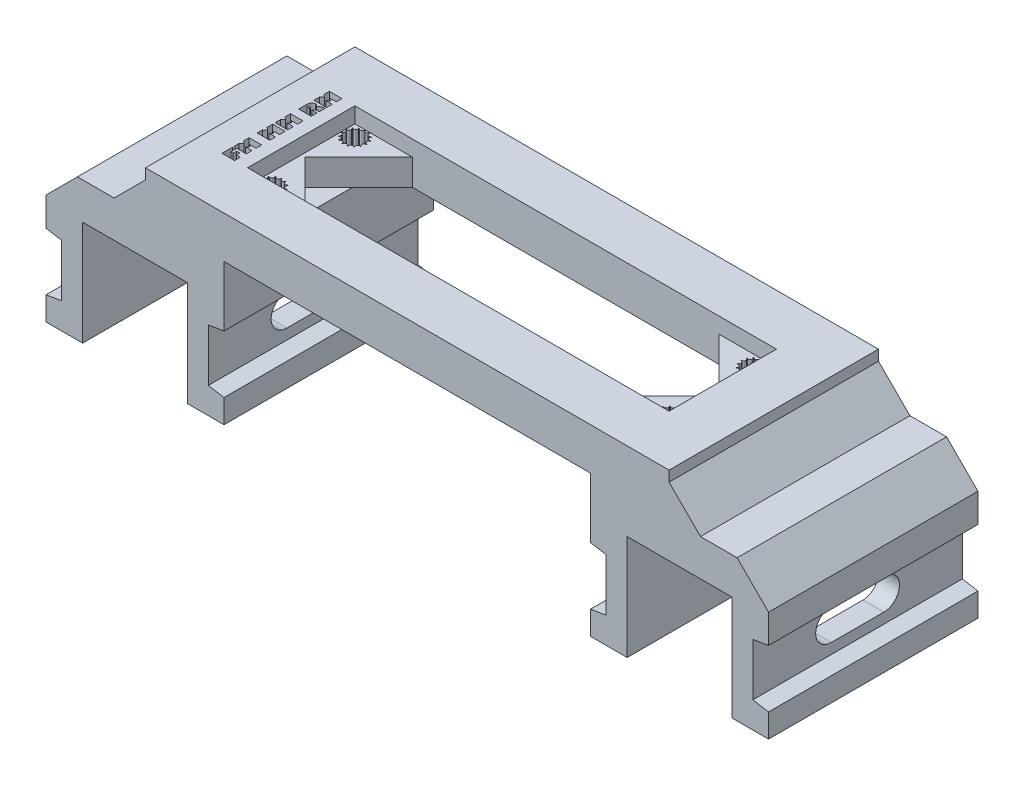
SolidWorks part; units mm, degrees
ref_plane "Front Plane" through (0, 0, 0) normal (0, 0, 1) x (1, 0, 0)
ref_plane "Top Plane" through (0, 0, 0) normal (0, 1, 0) x (1, 0, 0)
ref_plane "Right Plane" through (0, 0, 0) normal (1, 0, 0) x (0, 0, -1)
sketch "Sketch1" plane through (0, 0, 0) normal (0, 1, 0) x (1, 0, 0)
  line L1 (0, 0) -> (80, 0)
  line L2 (0, 0) -> (0, 20)
  line L3 (0, 20) -> (80, 20)
  line L4 (80, 0) -> (80, 20)
  dimension "D1" = 20
  dimension "D2" = 80
extrude "Boss-Extrude1" add sketch "Sketch1" along normal blind 8
sketch "Sketch2" plane through (0, 8, 0) normal (0, 1, 0) x (1, 0, 0)
  line L0 (0, 0) -> (80, 0) construction
  line L1 (0, 10) -> (80, 10) construction
  line L2 (0, 20) -> (0, 0) construction
  line L3 (5.4641, 0) -> (0, 0)
  line L4 (0, 0) -> (0, 5.4641)
  line L5 (80, 0) -> (80, 20) construction
  line L6 (80, 10) -> (40, 10) construction
  line L7 (40, 10) -> (40, 20) construction
  line L8 (80, 20) -> (0, 20) construction
  line L13 (0, 20) -> (0, 0)
  line L14 (0, 0) -> (80, 0)
  line L15 (80, 0) -> (80, 20)
  line L16 (80, 20) -> (0, 20)
  line L17 (0, 20) -> (0, 0)
  line L18 (0, 0) -> (80, 0)
  line L19 (80, 0) -> (80, 20)
  line L20 (80, 20) -> (0, 20)
  circle A0 centre (2, 2) radius 2.25
  arc A1 (5.4641, 0) -> (0, 5.4641) centre (2, 2) ccw
  arc A2 (5.4641, 20) -> (0, 14.5359) centre (2, 18) cw
  circle A3 centre (2, 18) radius 2.25
  arc A4 (74.5359, 20) -> (80, 14.5359) centre (78, 18) ccw
  arc A5 (74.5359, 0) -> (80, 5.4641) centre (78, 2) cw
  circle A6 centre (-0.25, 2) radius 0.4
  circle A7 centre (-0.0555, 2.9152) radius 0.4
  circle A8 centre (0.4945, 3.6721) radius 0.4
  circle A9 centre (1.3047, 4.1399) radius 0.4
  circle A10 centre (2.2352, 4.2377) radius 0.4
  circle A11 centre (3.125, 3.9486) radius 0.4
  circle A12 centre (3.8203, 3.3225) radius 0.4
  circle A13 centre (4.2008, 2.4678) radius 0.4
  circle A14 centre (4.2008, 1.5322) radius 0.4
  circle A15 centre (3.8203, 0.6775) radius 0.4
  circle A16 centre (3.125, 0.0514) radius 0.4
  circle A17 centre (2.2352, -0.2377) radius 0.4
  circle A18 centre (1.3047, -0.1399) radius 0.4
  circle A19 centre (0.4945, 0.3279) radius 0.4
  circle A20 centre (-0.0555, 1.0848) radius 0.4
  point P64 (2, 2)
  line M11 (0, 20) -> (0, 0)
  line M12 (0, 0) -> (80, 0)
  dimension "D1" = 4.5
  dimension "D4" = 8
  dimension "D6" = 0.8
  dimension "D2" = 2
  dimension "D3" = 2
  dimension "D5" = 0
  dimension "D7" = 15
extrude "Cut-Extrude1" cut sketch "Sketch2" against normal blind 8 contours A5 L19 A4 L20 A2 L17 A1 M12 region at (40, 8, -10)
sketch "Sketch3" plane through (0, 8, 0) normal (0, 1, 0) x (1, 0, 0)
  line L0 (90, -10) -> (90, 30)
  line L1 (80, 0) -> (0, 0)
  line L2 (80, 0) -> (80, 20)
  line L3 (80, 20) -> (0, 20)
  line L4 (0, 0) -> (0, 20)
  line L5 (90, 30) -> (-10, 30)
  line L6 (-10, -10) -> (-10, 30)
  line L7 (90, -10) -> (-10, -10)
  dimension "D1" = 10
extrude "Boss-Extrude2" add sketch "Sketch3" against normal blind 8
extrude "Cut-Extrude2" cut sketch "Sketch2<3>" against normal blind 12 contours A20 A0 A19 A18 A17 L18 A16 A15 A14 A13 A12 A11 A10 A9 A8 A7 A6 L17 M12 M11 | A20 L17 A6 A0 | A7 A0 A6 M11 | A18 A0 A17 M12 | A17 A0 A16 L18 region at (2.6664, 8, 0.0685) region at (2.0103, 8, -2.0102) region at (-0.0939, 8, -2.4404) region at (1.7813, 8, 0.1077) region at (-0.0939, 8, -1.5596)
sketch "Sketch2<3>" plane through (0, 8, 0) normal (0, 1, 0) x (1, 0, 0) same geometry as "Sketch2"
ref_plane "Plane1" through (40, 0, 0) normal (-1, 0, 0) x (0, 0, 1)
ref_plane "Plane2" through (0, 0, -10) normal (0, 0, 1) x (1, 0, 0)
mirror "Mirror1" about plane through (0, 0, -10) normal (0, 0, 1) of "Cut-Extrude2" second plane through (40, 0, 0) second plane normal (-1, 0, 0)
sketch "Sketch4" plane through (0, 0, 0) normal (0, -1, 0) x (1, 0, 0)
  line L0 (40, -30) -> (40, 10) construction
  line L1 (90, -30) -> (-10, -30) construction
  line L2 (-10, 10) -> (90, 10) construction
  line L3 (40, 4.4) -> (40, -4.4) construction
  line L4 (5, -30) -> (-29, -30)
  line L5 (5, -30) -> (5, 10)
  line L6 (5, 10) -> (-29, 10)
  line L7 (-29, -30) -> (-29, 10)
  dimension "D1" = 35
  dimension "D2" = 34
extrude "Boss-Extrude3" add sketch "Sketch4" along normal blind 27 and the other way blind 0.0001
sketch "Sketch5" plane through (0, 0, -30) normal (0, 0, -1) x (-1, 0, 0)
  line L1 (29, -27) -> (29, 0.0001) construction
  line L2 (-5, -27) -> (-5, 0) construction
  line L10 (29, 0.0001) -> (10, 0.0001) construction
  line L11 (29, -27) -> (29, 0.0001)
  line L13 (29, 0.0001) -> (10, 0.0001)
  line L14 (22, -27) -> (22, -6.9999)
  line L15 (22, -6.9999) -> (2, -6.9999)
  line L16 (2, -27) -> (2, -6.9999)
  line L17 (22, -6.9999) -> (10, -6.9999) construction
  line L19 (22, -27) -> (2, -27)
  line M12 (-5, -27) -> (29, -27)
  dimension "D2" = 7
  dimension "D1" = 7
extrude "Cut-Extrude3" cut sketch "Sketch5" against normal blind 51 contours L16 L14 L15 M12 region at (-12, -17, -30)
sketch "Sketch6" plane through (0, 0, -30) normal (0, 0, -1) x (-1, 0, 0)
  line L0 (22, -16.9999) -> (2, -16.9999) construction
  line L1 (22, -27) -> (22, -6.9999) construction
  line L2 (2, -27) -> (2, -6.9999) construction
  line L3 (29, -27) -> (29, 0.0001) construction
  line L5 (29, -11.4999) -> (29, -22.5)
  line L7 (26, -11.9999) -> (26, -22)
  line L8 (22, -16.9999) -> (29, -16.9999) construction
  line L9 (26, -11.9999) -> (29, -11.4999)
  line L11 (26, -22) -> (29, -22.5)
  point P13 (29, -16.9999)
  point P16 (27.1641, -12.6969)
  point P17 (29, -23.9999)
  point P20 (29, -23.9999)
  dimension "D2" = 3
  dimension "D3" = 10
extrude "Cut-Extrude4" cut sketch "Sketch6" against normal blind 51
ref_plane "Plane3" through (-12, 0, 0) normal (1, 0, 0) x (0, 0, -1)
mirror "Mirror2" about plane through (-12, 0, 0) normal (1, 0, 0) of "Cut-Extrude4"
mirror "Mirror3" about plane through (40, 0, 0) normal (-1, 0, 0) of "Boss-Extrude3", "Cut-Extrude3", "Cut-Extrude4", "Mirror2"
fillet "Fillet1" radius 6 4 edges at (109, 0.0001, -10) (90, 0.0001, -10) (-29, 0.0001, -10) (-10, 0.0001, -10) profile chamfer
sketch "Sketch7" plane through (-26, 0, 0) normal (-1, 0, 0) x (0, 0, 1)
  line L0 (10, -16.9999) -> (-30, -17) construction
  line L1 (10, -22) -> (10, -11.9999) construction
  line L2 (-30, -11.9999) -> (-30, -22) construction
  line L3 (-5, -17) -> (-15, -17) construction
  line L4 (-5, -20) -> (-15, -20)
  line L5 (-5, -14) -> (-15, -14)
  arc A0 (-5, -20) -> (-5, -14) centre (-5, -17) ccw
  arc A1 (-15, -14) -> (-15, -20) centre (-15, -17) ccw
  point P8 (-10, -17)
  dimension "D1" = 15
  dimension "D2" = 10
  dimension "D3" = 6
extrude "Cut-Extrude5" cut sketch "Sketch7" against normal blind 160 contours A0 L5 A1 L4
sketch "Sketch8" plane through (0, 8, 0) normal (0, 1, 0) x (1, 0, 0)
  line L0 (40, 20) -> (40, 0) construction
  line L1 (74.5359, 20) -> (5.4641, 20) construction
  line L2 (5.4641, 0) -> (74.5359, 0) construction
  line L3 (40, 0) -> (48.8441, 10) construction
  line L4 (-19.25, 10) -> (19.25, 10) construction
  line L5 (48.8441, 10) -> (40, 10) construction
  line L7 (-0.25, -0.25) -> (80.25, -0.25)
  line L8 (-0.25, -0.25) -> (-0.25, 20.25)
  line L9 (-0.25, 20.25) -> (80.25, 20.25)
  line L10 (80.25, -0.25) -> (80.25, 20.25)
  line L11 (-0.25, -0.25) -> (80.25, 20.25) construction
  line L12 (-0.25, 20.25) -> (80.25, -0.25) construction
  dimension "D1" = 80.5
  dimension "D2" = 20.5
extrude "Cut-Extrude6" cut sketch "Sketch8" against normal blind 3
sketch "Sketch10" plane through (0, 5, 0) normal (0, 1, 0) x (1, 0, 0)
  line L4 (80.25, -0.25) -> (80.25, 20.25)
  line L5 (80.25, 20.25) -> (-0.25, 20.25)
  line L6 (-0.25, 20.25) -> (-0.25, -0.25)
  line L7 (-0.25, -0.25) -> (80.25, -0.25)
  line L8 (80.25, -0.25) -> (80.25, 20.25)
  line L9 (80.25, 20.25) -> (-0.25, 20.25)
  line L10 (-0.25, 20.25) -> (-0.25, -0.25)
  line L11 (-0.25, -0.25) -> (80.25, -0.25)
  circle A0 centre (2, 18) radius 4
  circle A1 centre (78, 18) radius 4
  circle A2 centre (78, 2) radius 4
  circle A3 centre (2, 2) radius 4
  dimension "D1" = 0
extrude "Cut-Extrude8" cut sketch "Sketch10" against normal up to surface (5 mm away) contours A3 L11 A2 L8 A1 L9 A0 L10 region at (40, 5, -10) up to face at (40, 0, -21.7598)
sketch "Sketch11" plane through (0, 5, 0) normal (0, 1, 0) x (1, 0, 0)
  line L0 (80.25, 10.75) -> (69.25, -0.25)
  line L1 (80.25, -0.25) -> (80.25, 20.25) construction
  line L2 (-0.25, -0.25) -> (80.25, -0.25) construction
  line L3 (80.25, 5.3072) -> (80.25, 14.6928) construction
  line L4 (80.25, 10.75) -> (80.25, -0.25)
  line L5 (80.25, -0.25) -> (69.25, -0.25)
  arc A0 (80.25, 5.3072) -> (74.6928, -0.25) centre (78, 2) ccw construction
  arc A1 (80.25, 5.3072) -> (74.6928, -0.25) centre (78, 2) ccw
  arc M34 (80.25, 5.3072) -> (74.6928, -0.25) centre (78, 2) ccw
  dimension "D1" = 11
  dimension "D2" = 11
extrude "Boss-Extrude4" add sketch "Sketch11" against normal up to surface (5 mm away) contours L5 L4 L0 M34 region at (80.0944, 5, -8.0286) up to face at (77.5625, 0, -10)
mirror "Mirror6" about plane through (40, 0, 0) normal (-1, 0, 0) of "Boss-Extrude4"
mirror "Mirror7" about plane through (0, 0, -10) normal (0, 0, 1) of "Mirror6"
sketch "Sketch12" plane through (0, 8, 0) normal (0, 1, 0) x (1, 0, 0)
  line L0 (-0.25, 10) -> (-8.7736, 10) construction
  line L1 (-0.25, 20.25) -> (-0.25, -0.25) construction
  line L2 (-19.25, 10) -> (19.25, 10) construction
  line L3 (-2.6841, -0.5313) -> (-2.6841, 20.0653) construction
  text T0 "FM MM RM" font "Gill Sans Ultra Bold" height 2.4
  point P9 (-2.6841, -0.5313)
extrude "Cut-Extrude9" cut sketch "Sketch12" against normal blind 2
